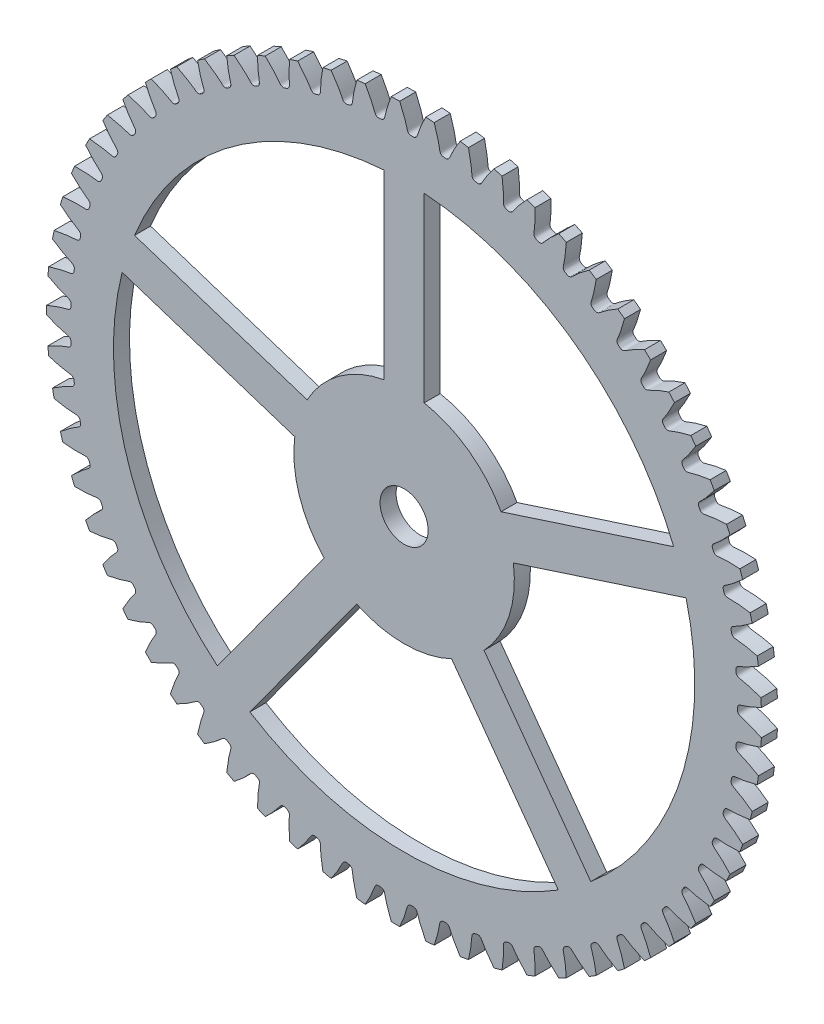
SolidWorks part; units mm, degrees
ref_plane "Alzado" through (0, 0, 0) normal (0, 0, 1) x (1, 0, 0)
ref_plane "Planta" through (0, 0, 0) normal (0, 1, 0) x (1, 0, 0)
ref_plane "Vista lateral" through (0, 0, 0) normal (1, 0, 0) x (0, 0, -1)
ref_axis "Eje1" through (0, 0, 55) along (0, 0, -1)
sketch "SketchRevolveEngranaje Arriba(8.9)" plane through (0, 0, 0) normal (1, 0, 0) x (0, 0, -1)
  line L0 (0, 0) -> (1, 0) construction
  line L1 (-0.1, 0) -> (-0.1, 4.4581)
  line L2 (-0.1, 4.4581) -> (0.1, 4.4581)
  line L3 (0.1, 4.4581) -> (0.1, 0)
  line L4 (0.1, 0) -> (-0.1, 0)
revolve "Engranaje Arriba(8.9)" add sketch "SketchRevolveEngranaje Arriba(8.9)" angle 360 about L0
sketch "SketchToothEngranaje Arriba(8.9)" plane through (0, 0, 0) normal (0, 0, 1) x (1, 0, 0)
  arc A0 (4.4551, 0.1629) -> (4.4551, -0.1629) centre (0, 0) cw
  spline S0 degree 3 poles (4.4551, -0.1629) (4.4391, -0.155) (4.4179, -0.1448) (4.3915, -0.1329) (4.3763, -0.1262) (4.3614, -0.1198) (4.3469, -0.1138) (4.3326, -0.108) (4.3187, -0.1025) (4.3051, -0.0973) (4.2919, -0.0924) (4.279, -0.0878) (4.2664, -0.0835) (4.2542, -0.0794) (4.2424, -0.0755) (4.2309, -0.0719) (4.2184, -0.0682) (4.2089, -0.0652) (4.2021, -0.0635) (4.1994, -0.0626) (4.1966, -0.0618) (4.1939, -0.0608) (4.1912, -0.0597) (4.1884, -0.0585) (4.1856, -0.0571) (4.1828, -0.0555) (4.1798, -0.0537) (4.1767, -0.0514) (4.1735, -0.0487) (4.1701, -0.0453) (4.1667, -0.0411) (4.1635, -0.036) (4.1608, -0.0297) (4.159, -0.0227) (4.1584, -0.0127) (4.1589, 0) (4.1584, 0.0127) (4.159, 0.0227) (4.1608, 0.0297) (4.1635, 0.036) (4.1667, 0.0411) (4.1701, 0.0453) (4.1735, 0.0487) (4.1767, 0.0514) (4.1798, 0.0537) (4.1828, 0.0555) (4.1856, 0.0571) (4.1884, 0.0585) (4.1912, 0.0597) (4.1939, 0.0608) (4.1966, 0.0618) (4.1994, 0.0626) (4.2021, 0.0635) (4.2089, 0.0652) (4.2184, 0.0682) (4.2309, 0.0719) (4.2424, 0.0755) (4.2542, 0.0794) (4.2664, 0.0835) (4.279, 0.0878) (4.2919, 0.0924) (4.3051, 0.0973) (4.3187, 0.1025) (4.3326, 0.108) (4.3469, 0.1138) (4.3614, 0.1198) (4.3763, 0.1262) (4.3915, 0.1329) (4.4179, 0.1448) (4.4391, 0.155) (4.4551, 0.1629) knots 0 0 0 0 0.074782 0.098558 0.121757 0.144381 0.166429 0.187901 0.208797 0.229117 0.248861 0.268029 0.286621 0.304637 0.322078 0.338942 0.35523 0.37658 0.380633 0.384653 0.388662 0.39269 0.39677 0.400949 0.405281 0.409838 0.414709 0.420005 0.425862 0.432436 0.439895 0.448371 0.457907 0.468363 0.478462 0.5 0.521538 0.531637 0.542093 0.551629 0.560105 0.567564 0.574138 0.579995 0.585291 0.590162 0.594719 0.599051 0.60323 0.60731 0.611338 0.615347 0.619367 0.62342 0.64477 0.661058 0.677922 0.695363 0.713379 0.731971 0.751139 0.770883 0.791203 0.812099 0.833571 0.855619 0.878243 0.901442 0.925218 1 1 1 1
extrude "ToothExtrudeCutEngranaje Arriba(8.9)" cut sketch "SketchToothEngranaje Arriba(8.9)" against normal blind 0.1 and the other way blind 0.1
pattern_circular "PatternEngranaje Arriba(8.9)" count 65 every 5.538 about axis through (0, 0, 55) along (0, 0, -1) of "ToothExtrudeCutEngranaje Arriba(8.9)"
sketch "AuxiliarySketchEngranaje Arriba(8.9)" plane through (0, 0, 0) normal (0, 0, 1) x (1, 0, 0)
  circle A0 centre (0, 0) radius 4.325 construction
  circle A1 centre (0, 0) radius 4.0642 construction
  circle A2 centre (0, 0) radius 4.2026 construction
  circle A3 centre (0, 0) radius 4.4581 construction
  circle A4 centre (0, 0) radius 4.1587 construction
  dimension "PitchDiameter" = 8.65
  dimension "BaseDiameter" = 8.1283
  dimension "FormDiameter" = 8.4052
  dimension "MajorDiameter" = 8.9162
  dimension "MinorDiameter" = 8.3173
sketch "Croquis1" plane through (0, 0, 0.1) normal (0, 0, 1) x (1, 0, 0)
  line L0 (0, 0) -> (0, 3.625) construction
  line L1 (0, 0) -> (-3.4476, 1.1202) construction
  line L2 (0, 0) -> (-2.1307, -2.9327) construction
  line L3 (0, 0) -> (3.4476, 1.1202) construction
  line L4 (0, 0) -> (2.1307, -2.9327) construction
  line L5 (0.5925, -1.2408) -> (1.9285, -3.0796)
  line L15 (1.2087, 0.6556) -> (3.3703, 1.358)
  line L16 (1.3632, 0.1801) -> (3.5248, 0.8824)
  line L18 (0.997, -0.9469) -> (2.333, -2.7857)
  line L20 (-1.2087, 0.6556) -> (-3.3703, 1.358)
  line L22 (-1.3632, 0.1801) -> (-3.5248, 0.8824)
  line L24 (-0.997, -0.9469) -> (-2.333, -2.7857)
  line L26 (-0.5925, -1.2408) -> (-1.9285, -3.0796)
  line L28 (0.25, 1.3521) -> (0.25, 3.625)
  line L30 (-0.25, 1.3521) -> (-0.25, 3.625)
  circle A0 centre (0, 0) radius 0.3
  arc A1 (-1.3632, 0.1801) -> (-0.997, -0.9469) centre (0, 0) ccw
  arc A2 (3.3621, 1.3553) -> (0.25, 3.6164) centre (0, 0) ccw
  arc A3 (-0.5925, -1.2408) -> (0.5925, -1.2408) centre (0, 0) ccw
  arc A4 (0.997, -0.9469) -> (1.3632, 0.1801) centre (0, 0) ccw
  arc A5 (1.2087, 0.6556) -> (0.25, 1.3521) centre (0, 0) ccw
  arc A6 (-0.25, 1.3521) -> (-1.2087, 0.6556) centre (0, 0) ccw
  arc A7 (-0.25, 3.6164) -> (-3.3621, 1.3553) centre (0, 0) ccw
  arc A8 (-3.5166, 0.8798) -> (-2.3279, -2.7788) centre (0, 0) ccw
  arc A9 (-1.9234, -3.0727) -> (1.9234, -3.0727) centre (0, 0) ccw
  arc A10 (2.3279, -2.7788) -> (3.5166, 0.8798) centre (0, 0) ccw
  point P7 (0.25, 0)
  point P12 (0.0773, -0.2378)
  point P14 (-0.2023, -0.1469)
  point P16 (-0.2023, 0.1469)
  point P18 (0.0773, 0.2378)
  point P20 (-0.25, 0)
  point P22 (-0.0773, 0.2378)
  point P24 (0.2023, 0.1469)
  point P26 (0.2023, -0.1469)
  point P28 (-0.0773, -0.2378)
  dimension "D1" = 0.6
  dimension "D2" = 7.25
  dimension "D3" = 2.75
  dimension "D4" = 72
  dimension "D5" = 72
  dimension "D6" = 72
  dimension "D7" = 72
  dimension "D8" = 0.5
  dimension "D9" = 0.25
  dimension "D10" = 0.25
  dimension "D11" = 0.25
  dimension "D12" = 0.25
  dimension "D13" = 0.25
  dimension "D14" = 0.5
  dimension "D15" = 0.25
  dimension "D16" = 0.5
  dimension "D17" = 0.25
extrude "Cortar-Extruir1" cut sketch "Croquis1" against normal up to next contours L30 A7 L20 A6 | A5 L15 A2 L28 | L18 A10 L16 A4 | L26 A9 L5 A3 | L22 A8 L24 A1 | A0 region at (0, -2.5734, 0.1) region at (1.5126, 2.0819, 0.1) region at (2.4474, -0.7952, 0.1) region at (-1.5126, 2.0819, 0.1) region at (-2.4474, -0.7952, 0.1) region at (0, 0, 0.1)
